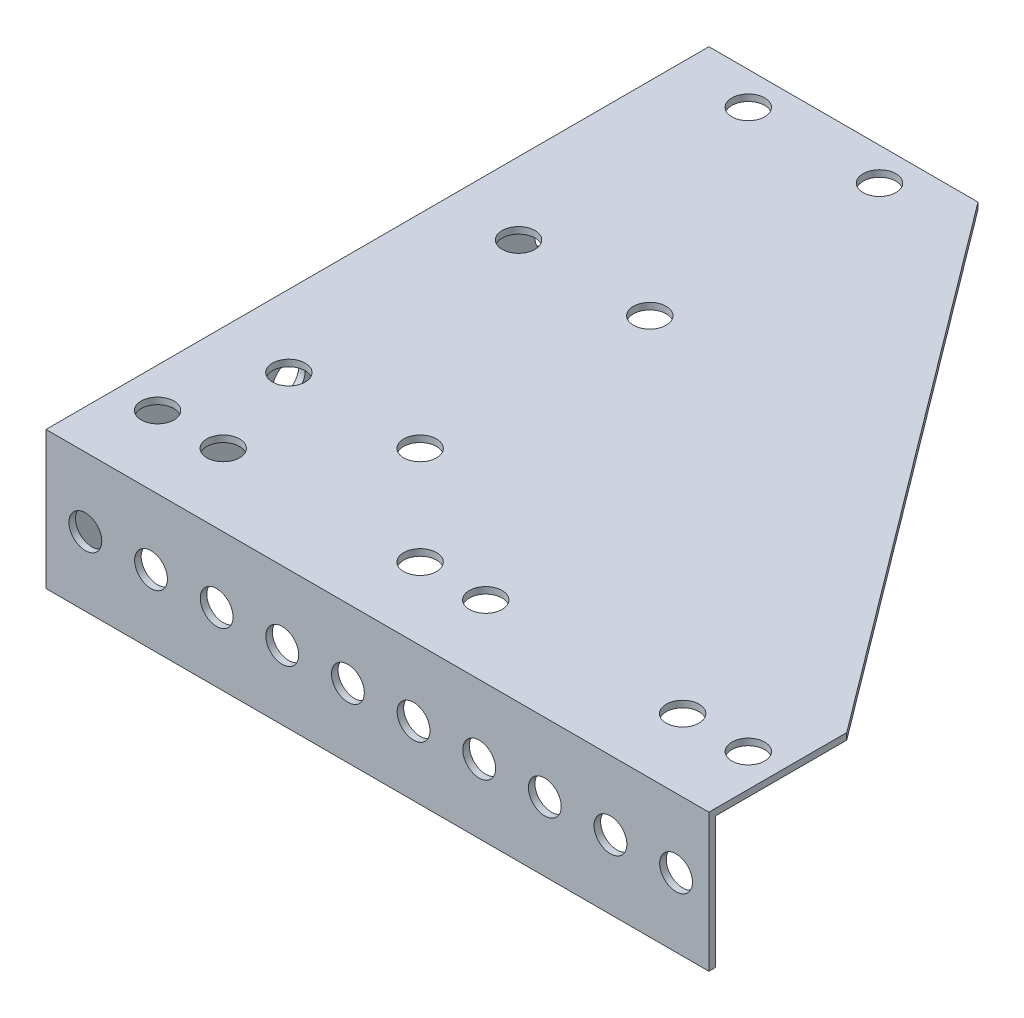
SolidWorks part; units mm, degrees
ref_plane "Front Plane" through (0, 0, 0) normal (0, 0, 1) x (1, 0, 0)
ref_plane "Top Plane" through (0, 0, 0) normal (0, 1, 0) x (1, 0, 0)
ref_plane "Right Plane" through (0, 0, 0) normal (1, 0, 0) x (0, 0, -1)
sketch "Sketch1" plane through (0, 0, 0) normal (0, 1, 0) x (1, 0, 0)
  line L0 (0, 0) -> (0, -100)
  line L1 (0, -100) -> (100, -100)
  line L2 (100, -100) -> (100, -80)
  line L3 (100, -80) -> (40, 0)
  line L4 (40, 0) -> (0, 0)
  line L5 (40, 0) -> (40, -80) construction
  line L6 (40, -80) -> (100, -80) construction
  line L7 (40, -5) -> (20, -5) construction
  line L8 (20, -5) -> (0, -5) construction
  line L9 (40, -40) -> (0, -40) construction
  line L10 (50, -80) -> (50, -100) construction
  line L11 (40, -5) -> (40, -40) construction
  line L12 (40, -22.5) -> (0, -22.5) construction
  line L13 (85, -90) -> (95, -90) construction
  line L14 (45, -90) -> (55, -90) construction
  circle A0 centre (10, -5) radius 2.5
  circle A1 centre (30, -5) radius 2.5
  circle A2 centre (85, -90) radius 2.5
  circle A3 centre (95, -90) radius 2.5
  circle A6 centre (30, -75) radius 2.5
  circle A7 centre (10, -75) radius 2.5
  circle A8 centre (5, -90) radius 2.5
  circle A9 centre (15, -90) radius 2.5
  circle A10 centre (30, -40) radius 2.5
  circle A11 centre (10, -40) radius 2.5
  circle A12 centre (45, -90) radius 2.5
  circle A13 centre (55, -90) radius 2.5
  point P19 (100, -90)
  point P32 (50, -100)
  point P40 (50, -90)
  dimension "D4" = 5
  dimension "D6" = 5
  dimension "D7" = 10
  dimension "D8" = 5
  dimension "D1" = 40
  dimension "D2" = 20
  dimension "D3" = 100
  dimension "D5" = 5
extrude "Boss-Extrude1" add sketch "Sketch1" along normal blind 1
sketch "Sketch2" plane through (0, 0, 0) normal (-1, 0, 0) x (0, 0, 1)
  line L0 (0, 0) -> (100, 0) construction
  line L9 (100, 1) -> (0, 1)
  line L10 (100, 1) -> (100, -20)
  line L11 (100, -20) -> (0, -20)
  line L12 (0, 1) -> (0, -20)
  line L13 (0, 1) -> (0, 0) construction
  line L14 (5, -10) -> (15, -10) construction
  line L15 (5, -10) -> (0, -10) construction
  line L16 (75, -10) -> (80, -10) construction
  line L17 (80, 0) -> (80, -20) construction
  circle A0 centre (5, -10) radius 2.5
  circle A1 centre (15, -10) radius 2.5
  circle A2 centre (25, -10) radius 2.5
  circle A3 centre (35, -10) radius 2.5
  circle A4 centre (45, -10) radius 2.5
  circle A5 centre (55, -10) radius 2.5
  circle A6 centre (65, -10) radius 2.5
  circle A7 centre (75, -10) radius 2.5
  dimension "D4" = 5
  dimension "D1" = 20
  dimension "D3" = 10
  dimension "D5" = 20
  dimension "D2" = 8
extrude "Boss-Extrude2" add sketch "Sketch2" along normal blind 1
sketch "Sketch3" plane through (0, 0, 100) normal (0, 0, 1) x (1, 0, 0)
  line L0 (95, -9.5) -> (85, -9.5) construction
  line L1 (100, 1) -> (-1, 1)
  line L2 (100, 1) -> (100, -20)
  line L3 (100, -20) -> (-1, -20)
  line L4 (-1, 1) -> (-1, -20)
  line L5 (-1, -20) -> (-1, 1) construction
  line L6 (-1, -20) -> (0, -20) construction
  line L7 (95, -9.5) -> (100, -9.5) construction
  line L8 (5, -9.5) -> (0, -9.5) construction
  line L9 (0, -20) -> (0, 0) construction
  circle A0 centre (95, -9.5) radius 2.5
  circle A1 centre (85, -9.5) radius 2.5
  circle A2 centre (75, -9.5) radius 2.5
  circle A3 centre (65, -9.5) radius 2.5
  circle A4 centre (55, -9.5) radius 2.5
  circle A5 centre (45, -9.5) radius 2.5
  circle A6 centre (35, -9.5) radius 2.5
  circle A7 centre (25, -9.5) radius 2.5
  circle A8 centre (15, -9.5) radius 2.5
  circle A9 centre (5, -9.5) radius 2.5
  dimension "D3" = 5
  dimension "D2" = 10
  dimension "D1" = 10
extrude "Boss-Extrude5" add sketch "Sketch3" along normal blind 1
